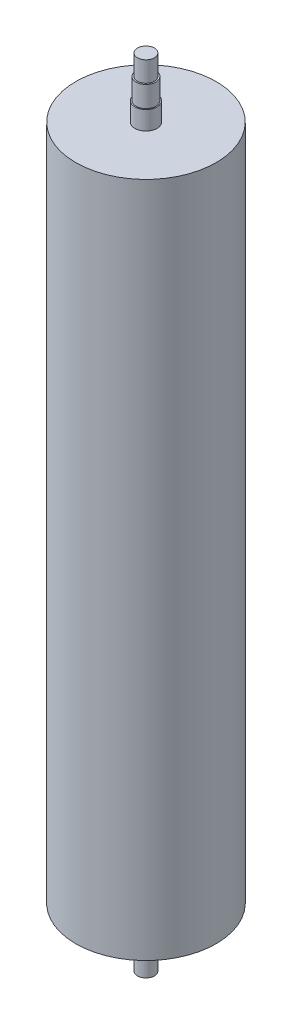
SolidWorks part; units mm, degrees
material "Stainless Steel (ferritic)"
ref_plane "Front Plane" through (0, 0, 0) normal (0, 0, 1) x (1, 0, 0)
ref_plane "Top Plane" through (0, 0, 0) normal (0, 1, 0) x (1, 0, 0)
ref_plane "Right Plane" through (0, 0, 0) normal (1, 0, 0) x (0, 0, -1)
sketch "Sketch1" plane through (0, 0, 0) normal (0, 1, 0) x (1, 0, 0)
  circle A0 centre (0, 0) radius 3.8495
  circle A1 centre (0, 0) radius 3.45
  circle A2 centre (0, 0) radius 2.95
  circle A3 centre (0, 0) radius 24.5
  dimension "D1" = 7.699
  dimension "D2" = 6.9
  dimension "D3" = 5.9
  dimension "D4" = 49
extrude "Boss-Extrude8" add sketch "Sketch1" along normal blind 236 contours A3
extrude "Boss-Extrude9" add sketch "Sketch1<9>" against normal blind 14 contours A0
sketch "Sketch1<9>" plane through (0, 0, 0) normal (0, 1, 0) x (1, 0, 0) same geometry as "Sketch1"
extrude "Boss-Extrude10" add sketch "Sketch1<10>" against normal blind 6.5 from surface contours A2 region at (0, 0, 0) starting at face at (0, -14, 3.8495)
sketch "Sketch1<10>" plane through (0, 0, 0) normal (0, 1, 0) x (1, 0, 0) same geometry as "Sketch1"
extrude "Boss-Extrude11" add sketch "Sketch1<11>" along normal blind 6.5 from surface contours A0 starting at face at (0, 236, 24.5)
sketch "Sketch1<11>" plane through (0, 0, 0) normal (0, 1, 0) x (1, 0, 0) same geometry as "Sketch1"
extrude "Boss-Extrude12" add sketch "Sketch1<12>" along normal blind 7.3 from surface contours A1 starting at face at (0, 242.5, 3.8495)
sketch "Sketch1<12>" plane through (0, 0, 0) normal (0, 1, 0) x (1, 0, 0) same geometry as "Sketch1"
extrude "Boss-Extrude13" add sketch "Sketch1<13>" along normal blind 7.1 from surface contours A2 starting at face at (0, 249.8, 3.45)
sketch "Sketch1<13>" plane through (0, 0, 0) normal (0, 1, 0) x (1, 0, 0) same geometry as "Sketch1"
